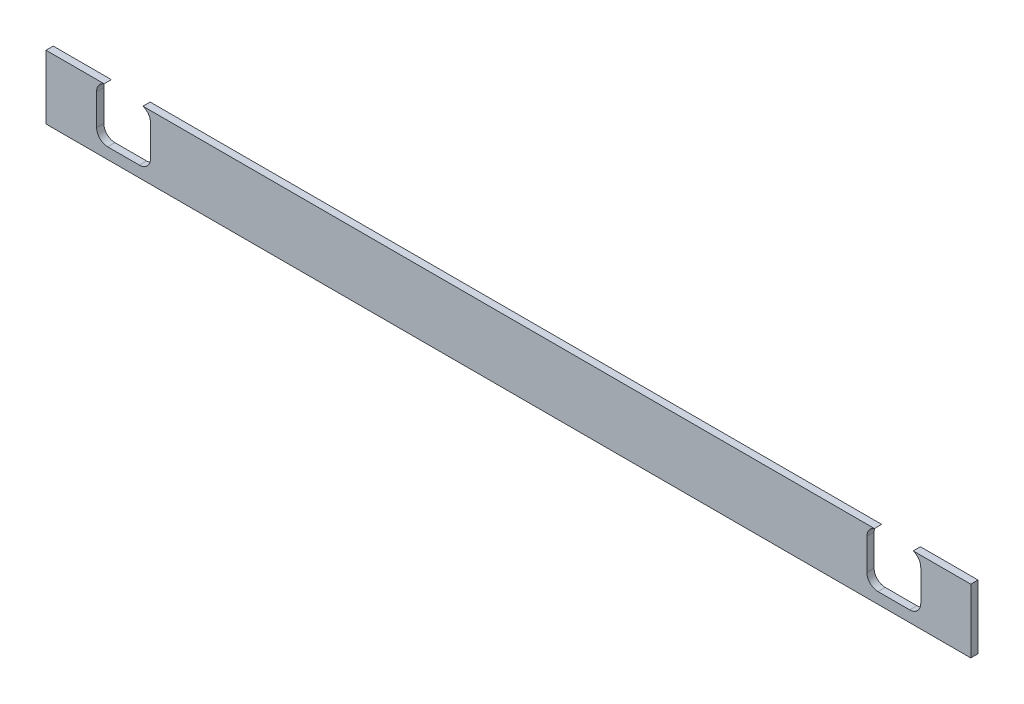
SolidWorks part; units mm, degrees
ref_plane "Plan de face" through (0, 0, 0) normal (0, 0, 1) x (1, 0, 0)
ref_plane "Plan de dessus" through (0, 0, 0) normal (0, 1, 0) x (1, 0, 0)
ref_plane "Plan de droite" through (0, 0, 0) normal (1, 0, 0) x (0, 0, -1)
sketch "Esquisse1" plane through (0, 0, 0) normal (0, 0, 1) x (1, 0, 0)
  line L1 (-416, -28.75) -> (416, -28.75)
  line L2 (-416, -28.75) -> (-416, 28.75)
  line L3 (-416, 28.75) -> (416, 28.75)
  line L4 (416, -28.75) -> (416, 28.75)
  line L5 (-416, -28.75) -> (416, 28.75) construction
  line L6 (-416, 28.75) -> (416, -28.75) construction
  point P0 (0, 0)
  dimension "D1" = 57.5
  dimension "D2" = 832
extrude "Boss.-Extru.1" add sketch "Esquisse1" along normal blind 6.5
sketch "Esquisse2" plane through (0, 0, 0) normal (0, 0, -1) x (-1, 0, 0)
  line L0 (416, -28.75) -> (-416, -28.75) construction
  line L1 (-361, -18.7714) -> (-332.526, -18.7714)
  line L2 (-371, -8.7714) -> (-371, 19.2748)
  line L3 (-361, 29.2748) -> (-332.526, 29.2748)
  line L4 (-322.526, -8.7714) -> (-322.526, 19.2748)
  line L5 (-371, -18.7714) -> (-322.526, 29.2748) construction
  line L6 (-371, 29.2748) -> (-322.526, -18.7714) construction
  line L7 (-416, -28.75) -> (-416, 28.75) construction
  arc A0 (-322.526, -8.7714) -> (-332.526, -18.7714) centre (-332.526, -8.7714) cw
  arc A1 (-361, -18.7714) -> (-371, -8.7714) centre (-361, -8.7714) cw
  arc A2 (-371, 19.2748) -> (-361, 29.2748) centre (-361, 19.2748) cw
  arc A3 (-322.526, 19.2748) -> (-332.526, 29.2748) centre (-332.526, 19.2748) ccw
  point P0 (-346.763, 5.2517)
  dimension "D1" = 10
  dimension "D2" = 9.9786
  dimension "D3" = 45
  dimension "D4" = 28.0461
extrude "Enlèv. mat.-Extru.1" cut sketch "Esquisse2" against normal through all
ref_axis "Axe1" through (390.0984, 28.75, 0) along (-0.9893, -0.1458, 0)
pattern_linear "Répétition linéaire1" count 2 spacing 693 along (-1, 0, 0) of "Enlèv. mat.-Extru.1"
